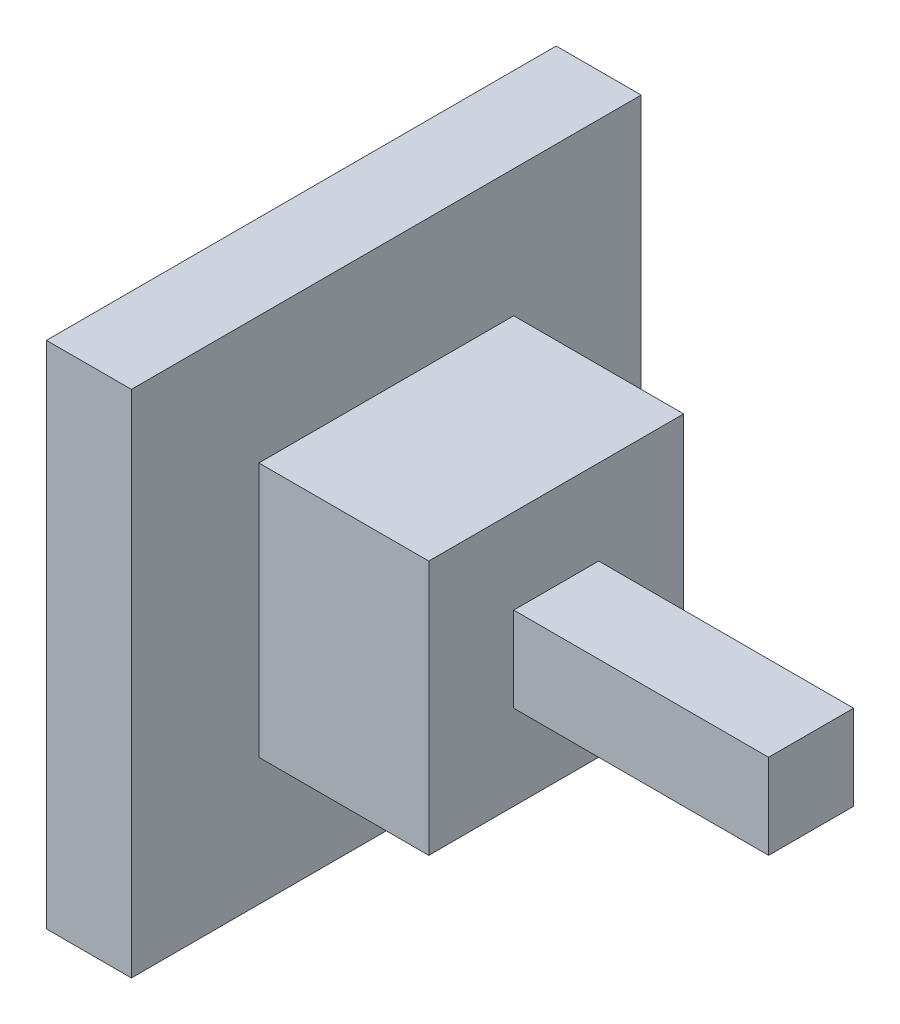
SolidWorks part; units mm, degrees
ref_plane "Front Plane" through (0, 0, 0) normal (0, 0, 1) x (1, 0, 0)
ref_plane "Top Plane" through (0, 0, 0) normal (0, 1, 0) x (1, 0, 0)
ref_plane "Right Plane" through (0, 0, 0) normal (1, 0, 0) x (0, 0, -1)
sketch "Sketch1" plane through (0, 0, 0) normal (1, 0, 0) x (0, 0, -1)
  line L1 (-12.7, -12.7) -> (12.7, -12.7)
  line L2 (-12.7, -12.7) -> (-12.7, 12.7)
  line L3 (-12.7, 12.7) -> (12.7, 12.7)
  line L4 (12.7, -12.7) -> (12.7, 12.7)
  line L5 (-12.7, -12.7) -> (12.7, 12.7) construction
  line L6 (-12.7, 12.7) -> (12.7, -12.7) construction
  line L7 (-38.1, -38.1) -> (38.1, -38.1)
  line L8 (-38.1, -38.1) -> (-38.1, 38.1)
  line L9 (-38.1, 38.1) -> (38.1, 38.1)
  line L10 (38.1, -38.1) -> (38.1, 38.1)
  line L11 (-38.1, -38.1) -> (38.1, 38.1) construction
  line L12 (-38.1, 38.1) -> (38.1, -38.1) construction
  line L13 (-76.2, -76.2) -> (76.2, -76.2)
  line L14 (-76.2, -76.2) -> (-76.2, 76.2)
  line L15 (-76.2, 76.2) -> (76.2, 76.2)
  line L16 (76.2, -76.2) -> (76.2, 76.2)
  line L17 (-76.2, -76.2) -> (76.2, 76.2) construction
  line L18 (-76.2, 76.2) -> (76.2, -76.2) construction
  point P0 (0, 0)
  point P6 (0, 0)
  point P11 (0, 0)
  dimension "D2" = 76.2
  dimension "D3" = 152.4
extrude "Boss-Extrude1" add sketch "Sketch1" along normal blind 152.4 contours L1 L4 L3 L2 region at (0, 0, 0)
extrude "Boss-Extrude2" add sketch "Sketch1<3>" along normal blind 76.2 separate body contours L7 L10 L9 L8 L4 L1 L2 L3 region at (0, 0, 37.0224)
sketch "Sketch1<3>" plane through (0, 0, 0) normal (1, 0, 0) x (0, 0, -1) same geometry as "Sketch1"
extrude "Boss-Extrude4" add sketch "Sketch1<5>" along normal blind 25.4 contours L14 L15 L16 L13
sketch "Sketch1<5>" plane through (0, 0, 0) normal (1, 0, 0) x (0, 0, -1) same geometry as "Sketch1"
equation "\"A\" = 1"
equation "\"B\"= \"A\" * 3"
equation "\"C\" = \"A\" * \"B\" * 2"
equation "\"D1@Sketch1\"=\"A\""
equation "\"D2@Sketch1\"=\"B\""
equation "\"D3@Sketch1\"=\"C\""
equation "\"D1@Boss-Extrude1\"=\"C\""
equation "\"D1@Boss-Extrude2\"=\"B\""
equation "\"D1@Boss-Extrude4\"=\"A\""
